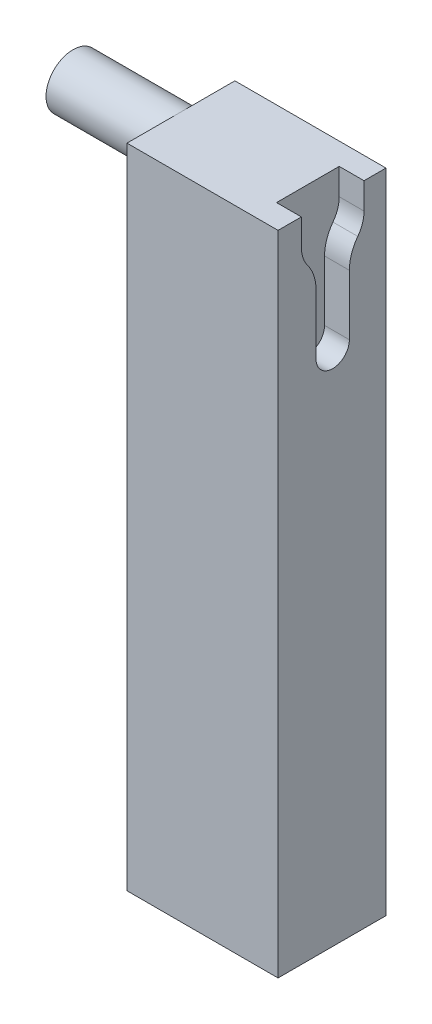
SolidWorks part; units mm, degrees
ref_plane "Front Plane" through (0, 0, 0) normal (0, 0, 1) x (1, 0, 0)
ref_plane "Top Plane" through (0, 0, 0) normal (0, 1, 0) x (1, 0, 0)
ref_plane "Right Plane" through (0, 0, 0) normal (1, 0, 0) x (0, 0, -1)
sketch "Sketch1" plane through (0, 0, 0) normal (0, 1, 0) x (1, 0, 0)
  line L1 (-17.78, -12.7) -> (17.78, -12.7)
  line L2 (-17.78, -12.7) -> (-17.78, 12.7)
  line L3 (-17.78, 12.7) -> (17.78, 12.7)
  line L4 (17.78, -12.7) -> (17.78, 12.7)
  line L5 (-17.78, -12.7) -> (17.78, 12.7) construction
  line L6 (-17.78, 12.7) -> (17.78, -12.7) construction
  point P0 (0, 0)
  dimension "D1" = 25.4
  dimension "D2" = 35.56
extrude "Boss-Extrude1" add sketch "Sketch1" along normal mid plane 50.8
sketch "Sketch2" plane through (-17.78, 0, 0) normal (-1, 0, 0) x (0, 0, 1)
  line L0 (-12.7, 25.4) -> (12.7, 25.4) construction
  circle A0 centre (0, 19.05) radius 6.35
  dimension "D1" = 12.7
extrude "Boss-Extrude2" add sketch "Sketch2" along normal mid plane 50.8
sketch "Sketch4" plane through (17.78, 0, 0) normal (1, 0, 0) x (0, 0, -1)
  line L0 (-3.64, 8.86) -> (-3.64, -5.29) construction
  line L1 (3.96, 8.86) -> (3.96, -5.29) construction
  line L2 (-3.64, 8.86) -> (-3.64, -5.29) construction
  line L3 (3.96, 8.86) -> (3.96, -5.29) construction
  line L4 (-3.767, 8.86) -> (-3.767, -5.29)
  line L5 (4.087, 8.86) -> (4.087, -5.29)
  line L6 (7.537, 19.21) -> (7.537, 26.587)
  line L7 (-7.217, 19.21) -> (-7.217, 26.587)
  line L8 (7.537, 26.587) -> (0.16, 26.587)
  line L9 (0.16, 26.587) -> (-7.217, 26.587)
  arc A0 (-3.64, 8.86) -> (-5.64, 14.86) centre (-13.64, 8.86) ccw construction
  arc A1 (-3.64, -5.29) -> (0.16, -9.09) centre (0.16, -5.29) ccw construction
  arc A3 (6.0616, 14.7838) -> (-5.7416, 14.7838) centre (0.16, 19.21) ccw
  arc A8 (6.8475, 16.41) -> (6.16, 23.2797) centre (0.16, 19.21) ccw construction
  arc A9 (-3.767, 8.86) -> (-5.7416, 14.7838) centre (-13.64, 8.86) ccw
  arc A10 (5.96, 14.86) -> (4.132, 10.7069) centre (13.96, 8.86) ccw construction
  arc A12 (-3.64, 8.86) -> (-5.64, 14.86) centre (-13.64, 8.86) ccw construction
  arc A13 (-3.64, -5.29) -> (3.96, -5.29) centre (0.16, -5.29) ccw construction
  arc A14 (-3.767, -5.29) -> (4.087, -5.29) centre (0.16, -5.29) ccw
  arc A15 (6.0616, 14.7838) -> (4.087, 8.86) centre (13.96, 8.86) ccw
  arc A20 (5.96, 14.86) -> (-5.64, 14.86) centre (0.16, 19.21) ccw construction
  arc A22 (5.96, 14.86) -> (3.96, 8.86) centre (13.96, 8.86) ccw construction
  point P5 (0.16, 26.587)
  line M5 (12.7, 25.4) -> (-12.7, 25.4)
  dimension "D1" = 0.127
extrude "Cut-Extrude1" cut sketch "Sketch4" against normal blind 5.842 contours A15 A3 A9 L4 A14 L5 M5 | A3 L6 L8 M5 | A3 L6 M5 | A3 L7 M5 | A3 L9 L7 M5 | A3 M5 region at (17.78, 10.5182, -0.16) region at (17.78, 23.9318, 6.2648) region at (17.78, 26.0609, 4.7948) region at (17.78, 25.8782, -0.16) region at (17.78, 26.0609, -5.1148) region at (17.78, 23.9318, -6.5848)
sketch "Sketch7" plane through (0, -25.4, 0) normal (0, -1, 0) x (1, 0, 0)
  line L1 (-17.78, 12.7) -> (17.78, 12.7)
  line L2 (-17.78, 12.7) -> (-17.78, -12.7)
  line L3 (-17.78, -12.7) -> (17.78, -12.7)
  line L4 (17.78, 12.7) -> (17.78, -12.7)
extrude "Boss-Extrude3" add sketch "Sketch7" along normal blind 101.6
